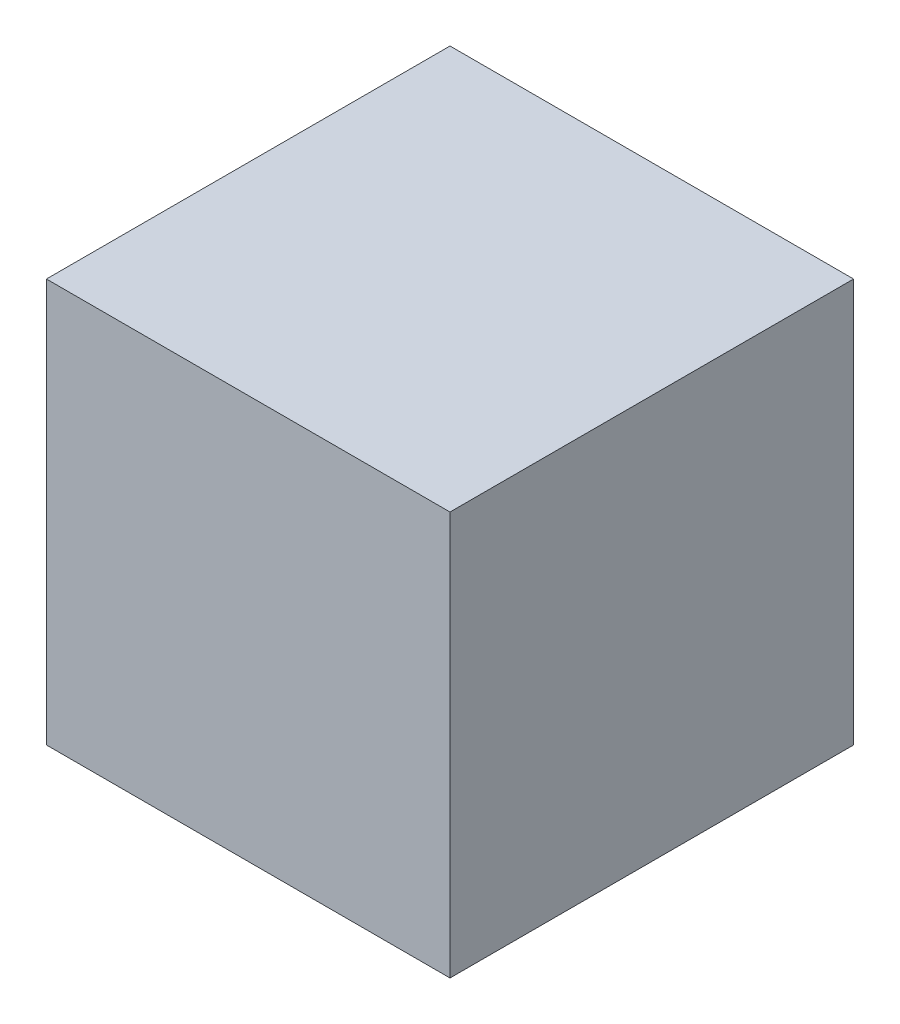
SolidWorks part; units mm, degrees
ref_plane "Front Plane" through (0, 0, 0) normal (0, 0, 1) x (1, 0, 0)
ref_plane "Top Plane" through (0, 0, 0) normal (0, 1, 0) x (1, 0, 0)
ref_plane "Right Plane" through (0, 0, 0) normal (1, 0, 0) x (0, 0, -1)
sketch "Sketch1" plane through (0, 0, 0) normal (0, 0, 1) x (1, 0, 0)
  line L7 (0, 0) -> (-1000, 0)
  line L8 (0, 0) -> (0, 1000)
  line L9 (0, 1000) -> (-1000, 1000)
  line L10 (-1000, 0) -> (-1000, 1000)
  dimension "D1" = 1000
  dimension "D2" = 1000
extrude "Boss-Extrude1" add sketch "Sketch1" along normal blind 1000
equation "\"height\"=1000"
equation "\"width\"=1000"
equation "\"D1@Sketch1\"=\"width\""
equation "\"D2@Sketch1\"=\"height\""
equation "\"length\"=1000"
equation "\"D1@Boss-Extrude1\"=\"length\""
